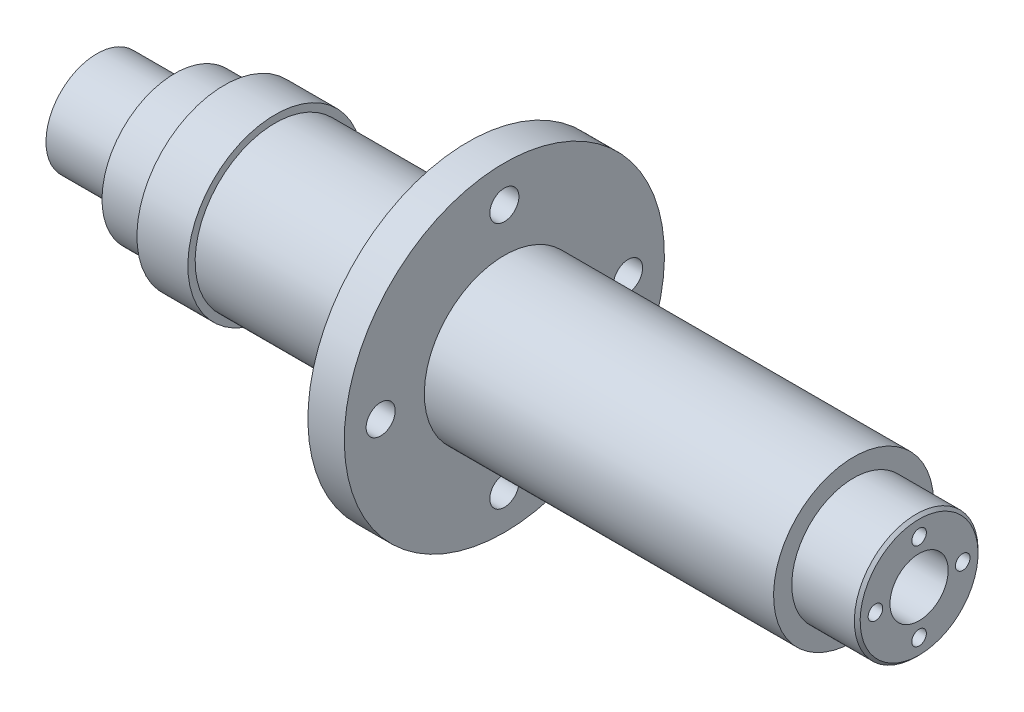
SolidWorks part; units mm, degrees
material "2024-T4"
ref_plane "Front Plane" through (0, 0, 0) normal (0, 0, 1) x (1, 0, 0)
ref_plane "Top Plane" through (0, 0, 0) normal (0, 1, 0) x (1, 0, 0)
ref_plane "Right Plane" through (0, 0, 0) normal (1, 0, 0) x (0, 0, -1)
other "Center of Mass" [suppressed]
sketch "Sketch3" plane through (0, 0, 0) normal (0, 0, 1) x (1, 0, 0)
  line L0 (0, 0) -> (0, 39.0464) construction
  line L1 (-75.5, 0) -> (75.5, 0) construction
  line L2 (-75.5, 2.5) -> (-75.5, 0) construction
  line L3 (-75.5, 2.5) -> (-75.5, 7)
  line L4 (-75.5, 7) -> (-65.3, 7)
  line L5 (-65.3, 7) -> (-65.3, 10)
  line L6 (-65.3, 10) -> (-58.5, 10)
  line L7 (-58.5, 10) -> (-58.5, 12)
  line L8 (-58.5, 12) -> (-41.5, 12)
  line L9 (-41.5, 12) -> (-41.5, 23)
  line L10 (-41.5, 23) -> (-29.5, 23)
  line L11 (-29.5, 23) -> (-29.5, 11)
  line L12 (-29.5, 11) -> (-24.5, 11)
  line L13 (0.5, 11) -> (0.5, 10)
  line L14 (0.5, 10) -> (38.5, 10)
  line L15 (38.5, 10) -> (38.5, 8.5)
  line L17 (75.5, 7.5) -> (75.5, 2.5)
  line L18 (75.5, 2.5) -> (-75.5, 2.5)
  line L19 (-35.5, 23) -> (-35.5, 2.5) construction
  line L20 (-11.5, 11) -> (-11.5, 2.5) construction
  line L21 (-77.5, 12) -> (-72.8417, 12) construction
  line L22 (-65.3, 10) -> (-65.3, 16) construction
  line L23 (-77.5, 15) -> (-72.8417, 15) construction
  line L24 (38.5, 8.5) -> (45.3, 8.5)
  line L25 (11.9511, 11) -> (20.8732, 11) construction
  line L26 (30.861, 12) -> (33.3773, 12) construction
  line L27 (45.3, 8.5) -> (45.3, 7.5)
  line L36 (45.3, 7.5) -> (75.5, 7.5)
  line L37 (-24.5, 11) -> (-24.5, 25)
  line L38 (38.5, 8.5) -> (44.5, 8.5) construction
  line L39 (-24.5, 25) -> (-19.5, 25)
  line L40 (-19.5, 25) -> (-19.5, 11)
  line L42 (-19.5, 11) -> (0.5, 11)
  point P5 (0, 0)
  dimension "D3" = 40
  dimension "D2" = 22
  dimension "D4" = 46
  dimension "D5" = 12
  dimension "D6" = 10.2
  dimension "D7" = 6.8
  dimension "D9" = 5
  dimension "D10" = 14
  dimension "D11" = 20
  dimension "D12" = 12
  dimension "D13" = 24
  dimension "D14" = 32
  dimension "D15" = 15
  dimension "D16" = 20
  dimension "D18" = 11
  dimension "D20" = 12
  dimension "D21" = 6.8
  dimension "D22" = 17
  dimension "D24" = 15
  dimension "D8" = 30
  dimension "D17" = 38
  dimension "D19" = 30.2
  dimension "D23" = 5
  dimension "D25" = 5
  dimension "D26" = 25
revolve "Revolve1" [suppressed] add sketch "Sketch3" angle 360 about L1
ref_plane "Plane1" [suppressed] through (0, 11, 0) normal (0, 1, 0) x (1, 0, 0)
sketch "Sketch4" [suppressed] plane through (0, 11, 0) normal (0, 1, 0) x (1, 0, 0)
  line L0 (0.5, 0) -> (-29.5, 0) construction
  line L1 (0.5, -11) -> (0.5, 11) construction
  line L2 (-29.5, -11) -> (-29.5, 11) construction
  line L3 (-14.5, 0) -> (-14.5, 23.5234) construction
  line L4 (75.5, -7.5) -> (75.5, 7.5) construction
  line L5 (75.5, 0) -> (65.5, 0) construction
  line L6 (-20.5, -2) -> (-8.5, -2)
  line L7 (-20.5, -2) -> (-20.5, 2)
  line L8 (-20.5, 2) -> (-8.5, 2)
  line L9 (-8.5, -2) -> (-8.5, 2)
  line L10 (-20.5, -2) -> (-8.5, 2) construction
  line L11 (-20.5, 2) -> (-8.5, -2) construction
  line L16 (59.5, -2) -> (71.5, -2)
  line L17 (59.5, -2) -> (59.5, 2)
  line L18 (59.5, 2) -> (71.5, 2)
  line L19 (71.5, -2) -> (71.5, 2)
  line L20 (59.5, -2) -> (71.5, 2) construction
  line L21 (59.5, 2) -> (71.5, -2) construction
  point P17 (65.5, 0)
  dimension "D1" = 12
  dimension "D2" = 4
  dimension "D3" = 10
  dimension "D4" = 12
  dimension "D5" = 4
fillet "Fillet1" [suppressed] radius 1
ref_plane "Plane2" [suppressed] through (0, 7.5, 0) normal (0, 1, 0) x (1, 0, 0)
sketch "Sketch5" [suppressed] plane through (0, 7.5, 0) normal (0, 1, 0) x (1, 0, 0)
  line L0 (71.5, -2) -> (71.5, 2) construction
  line L1 (59.5, -2) -> (71.5, -2) construction
  line L2 (59.5, -2) -> (59.5, 2) construction
  line L3 (59.5, 2) -> (71.5, 2) construction
  line L4 (71.5, -2) -> (71.5, 2)
  line L5 (59.5, -2) -> (71.5, -2)
  line L6 (59.5, -2) -> (59.5, 2)
  line L7 (59.5, 2) -> (71.5, 2)
sketch "Sketch6" plane through (0, 0, 0) normal (0, 0, 1) x (1, 0, 0)
  line L0 (-56.5, 0) -> (56.5, 0) construction
  line L1 (-56.5, 4) -> (-56.5, 7)
  line L2 (-56.5, 7) -> (-45.8, 7)
  line L3 (-45.8, 7) -> (-45.8, 10)
  line L4 (-45.8, 10) -> (-39, 10)
  line L5 (-39, 10) -> (-39, 12)
  line L6 (-39, 12) -> (-32, 12)
  line L7 (-32, 12) -> (-32, 11)
  line L8 (-32, 11) -> (-5.5, 11)
  line L9 (47.5, 11) -> (47.5, 8.5)
  line L10 (47.5, 8.5) -> (56.5, 8.5)
  line L11 (56.5, 8.5) -> (56.5, 4)
  line L12 (56.5, 4) -> (-56.5, 4)
  line L13 (4.5, 11) -> (4.5, 4) construction
  line L14 (-5.5, 11) -> (-5.5, 22)
  line L15 (-5.5, 22) -> (-0.5, 22)
  line L16 (-0.5, 22) -> (-0.5, 11)
  line L17 (-0.5, 11) -> (47.5, 11)
  point P4 (0, 0)
  dimension "D1" = 10.7
  dimension "D2" = 6.8
  dimension "D3" = 9
  dimension "D4" = 61
  dimension "D5" = 113
  dimension "D6" = 7
  dimension "D7" = 10
  dimension "D8" = 12
  dimension "D9" = 11
  dimension "D10" = 8.5
  dimension "D11" = 8
  dimension "D12" = 31.5
  dimension "D13" = 5
  dimension "D14" = 22
  dimension "D15" = 24.5
revolve "Revolve2" add sketch "Sketch6" angle 360 about L0
ref_plane "Plane3" through (0, 11, 0) normal (0, 1, 0) x (1, 0, 0)
sketch "Sketch8" [suppressed] plane through (-19.5, 0, 0) normal (1, 0, 0) x (0, 0, -1)
  line L0 (0, 0) -> (0, 17) construction
  circle A0 centre (0, 17) radius 2
  circle A1 centre (17, 0) radius 2
  circle A2 centre (0, -17) radius 2
  circle A3 centre (-17, 0) radius 2
  point P12 (0, 0)
  dimension "D1" = 4
  dimension "D3" = 17
  dimension "D4" = 17
  dimension "D5" = 34
  dimension "D2" = 4
extrude "Cut-Extrude5" [suppressed] cut sketch "Sketch8" against normal up to surface (5 mm away)
sketch "Sketch9" plane through (-0.5, 0, 0) normal (1, 0, 0) x (0, 0, -1)
  line L0 (0, 0) -> (0, 17) construction
  circle A0 centre (0, 17) radius 2
  circle A1 centre (17, 0) radius 2
  circle A2 centre (0, -17) radius 2
  circle A3 centre (-17, 0) radius 2
  point P12 (0, 0)
  dimension "D1" = 4
  dimension "D2" = 17
  dimension "D4" = 17
  dimension "D5" = 17
  dimension "D3" = 4
extrude "Cut-Extrude6" cut sketch "Sketch9" against normal up to surface (5 mm away) up to face at (-5.5, -11, 0)
sketch "Sketch10" [suppressed] plane through (75.5, 0, 0) normal (1, 0, 0) x (0, 0, -1)
  circle A1 centre (0, 0) radius 7.5 construction
  circle A2 centre (0, 0) radius 7.5
extrude "Cut-Extrude7" [suppressed] cut sketch "Sketch10" against normal blind 15
sketch "Sketch11" [suppressed] plane through (60.5, 0, 0) normal (1, 0, 0) x (0, 0, -1)
  line L0 (0, 0) -> (0, 5) construction
  circle A0 centre (0, 5) radius 1.5
  circle A1 centre (5, 0) radius 1.5
  circle A2 centre (0, -5) radius 1.5
  circle A3 centre (-5, 0) radius 1.5
  point P12 (0, 0)
  dimension "D1" = 3
  dimension "D3" = 5
  dimension "D2" = 4
extrude "Cut-Extrude8" [suppressed] cut sketch "Sketch11" against normal blind 10
chamfer "Chamfer1" [suppressed] distance 3 angle 45
sketch "Sketch12" plane through (56.5, 0, 0) normal (1, 0, 0) x (0, 0, -1)
  line L0 (0, 0) -> (0, 6) construction
  circle A0 centre (0, 6) radius 1
  circle A1 centre (6, 0) radius 1
  circle A2 centre (0, -6) radius 1
  circle A3 centre (-6, 0) radius 1
  point P13 (0, 0)
  dimension "D2" = 2
  dimension "D1" = 6
  dimension "D3" = 4
extrude "Cut-Extrude9" cut sketch "Sketch12" against normal blind 7
chamfer "Chamfer2" distance 0.4 angle 45 1 edges at (56.5, -8.5, 0)
equation "\"mainShaft-D\"= 20mm"
equation "\"mainTrackGear-D\"= 40mm"
equation "\"D4@Sketch3\"=\"wormGearL-D\""
equation "\"D11@Sketch3\"=\"mainShaft-D\""
equation "\"mini-flipper-shaft-diameter\"= 26mm"
equation "\"mini-shaft-ring-groove-diam\"= 7.8mm"
equation "\"mini-shaft-ring-groove-width\"= 1mm"
equation "\"dtCoverPlate-DistFrom-GearCent\"= 73mm"
equation "\"wormGearShaft-L\"= \"dtCoverPlate-DistFrom-GearCent\" - 27.75 + 3.75"
equation "\"wormGearShaft-Dsmall\"= 6mm"
equation "\"wormGearShaft-Dworm\"= 12mm"
equation "\"wormL-D\" = 12mm"
equation "\"wormR-D\" = 15mm"
equation "\"wormGearL-D\" = 46mm"
equation "\"wormGearR-D\" = 50mm"
